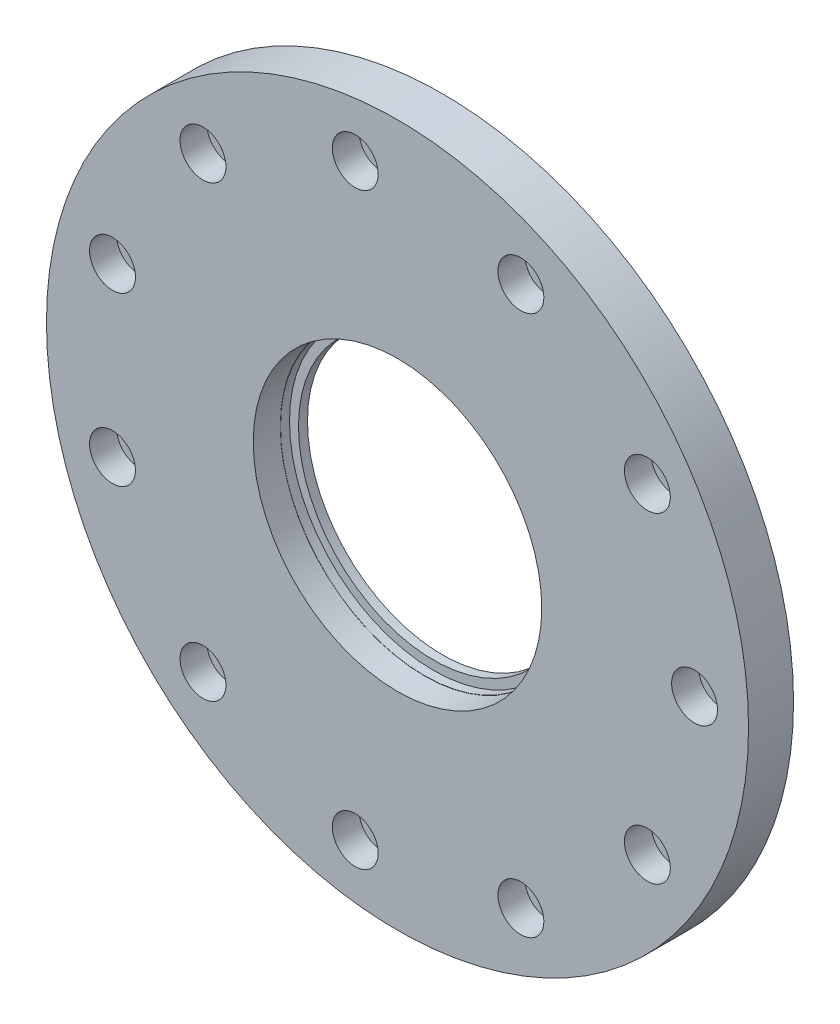
SolidWorks part; units mm, degrees
ref_plane "Front Plane" through (0, 0, 0) normal (0, 0, 1) x (1, 0, 0)
ref_plane "Top Plane" through (0, 0, 0) normal (0, 1, 0) x (1, 0, 0)
ref_plane "Right Plane" through (0, 0, 0) normal (1, 0, 0) x (0, 0, -1)
sketch "Sketch1" plane through (0, 0, 0) normal (0, 0, 1) x (1, 0, 0)
  circle A0 centre (0, 0) radius 39
  circle A1 centre (0, 0) radius 33 construction
  circle A2 centre (33, 0) radius 2.55
  circle A3 centre (27.7614, -17.8411) radius 2.55
  circle A4 centre (13.7087, -30.0179) radius 2.55
  circle A5 centre (-4.6964, -32.6641) radius 2.55
  circle A6 centre (-21.6104, -24.9397) radius 2.55
  circle A7 centre (-31.6633, -9.2972) radius 2.55
  circle A8 centre (-31.6633, 9.2972) radius 2.55
  circle A9 centre (-21.6104, 24.9397) radius 2.55
  circle A10 centre (-4.6964, 32.6641) radius 2.55
  circle A11 centre (13.7087, 30.0179) radius 2.55
  circle A12 centre (27.7614, 17.8411) radius 2.55
  circle A13 centre (0, 0) radius 16.025
  point P28 (0, 0)
extrude "Boss-Extrude1" add sketch "Sketch1" along normal blind 3
sketch "Sketch2" plane through (0, 0, 0) normal (0, 0, -1) x (-1, 0, 0)
  circle A0 centre (0, 0) radius 16
  circle A1 centre (0, 0) radius 39
  dimension "D1" = 32
extrude "Boss-Extrude2" add sketch "Sketch2" along normal blind 2 contours A1 | A0
sketch "Sketch3" plane through (0, 0, 3) normal (0, 0, 1) x (1, 0, 0)
  circle A0 centre (33, 0) radius 1.6
  circle A1 centre (27.7614, -17.8411) radius 1.6
  circle A2 centre (13.7087, -30.0179) radius 1.6
  circle A3 centre (-4.6964, -32.6641) radius 1.6
  circle A4 centre (-21.6104, -24.9397) radius 1.6
  circle A5 centre (-31.6633, -9.2972) radius 1.6
  circle A6 centre (-31.6633, 9.2972) radius 1.6
  circle A7 centre (-21.6104, 24.9397) radius 1.6
  circle A8 centre (-4.6964, 32.6641) radius 1.6
  circle A9 centre (13.7087, 30.0179) radius 1.6
  circle A10 centre (27.7614, 17.8411) radius 1.6
  point P25 (0, 0)
  dimension "D1" = 3.2
  dimension "D2" = 11
extrude "Cut-Extrude1" cut sketch "Sketch3" against normal through all
sketch "Sketch4" plane through (0, 0, -2) normal (0, 0, -1) x (-1, 0, 0)
  circle A0 centre (0, 0) radius 16
  circle A1 centre (0, 0) radius 15
  dimension "D1" = 32
  dimension "D2" = 30
extrude "Boss-Extrude3" add sketch "Sketch4" against normal blind 1
